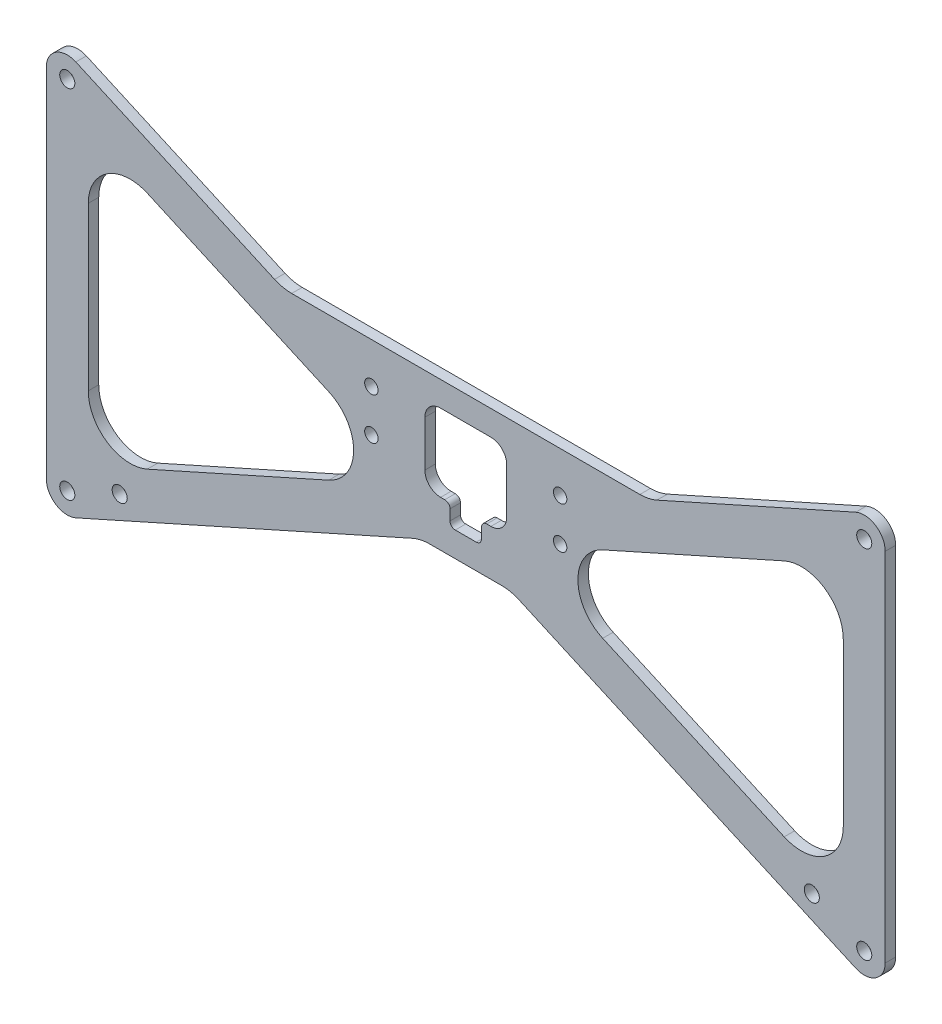
SolidWorks part; units mm, degrees
ref_plane "Front Plane" through (0, 0, 0) normal (0, 0, 1) x (1, 0, 0)
ref_plane "Top Plane" through (0, 0, 0) normal (0, 1, 0) x (1, 0, 0)
ref_plane "Right Plane" through (0, 0, 0) normal (1, 0, 0) x (0, 0, -1)
sketch "Sketch1" plane through (0, 0, 0) normal (0, 0, 1) x (1, 0, 0)
  line L0 (-120.65, -53.975) -> (120.65, 53.975) construction
  line L3 (-114.3, -44.1777) -> (-15.5498, 0)
  line L10 (-118.0569, -59.7714) -> (-13.6323, -13.0552)
  line L11 (-120.65, 53.975) -> (120.65, -53.975) construction
  line L12 (-118.0569, 59.7714) -> (-55.4208, 31.75)
  line L13 (-114.3, 44.1777) -> (-15.5498, 0)
  line L14 (55.4208, 31.75) -> (118.0569, 59.7714)
  line L15 (13.6323, -13.0552) -> (118.0569, -59.7714)
  line L16 (15.5498, 0) -> (114.3, 44.1777)
  line L17 (15.5498, 0) -> (114.3, -44.1777)
  line L18 (-127, 53.975) -> (-127, -53.975)
  line L19 (-114.3, 44.1777) -> (-114.3, -44.1777)
  line L20 (127, 53.975) -> (127, -53.975)
  line L21 (114.3, 44.1777) -> (114.3, -44.1777)
  line L24 (-55.4208, 31.75) -> (55.4208, 31.75)
  line L25 (-13.6323, -13.0552) -> (13.6323, -13.0552)
  arc A4 (-127, -53.975) -> (-118.0569, -59.7714) centre (-120.65, -53.975) ccw
  arc A5 (127, 53.975) -> (118.0569, 59.7714) centre (120.65, 53.975) ccw
  arc A6 (-118.0569, 59.7714) -> (-127, 53.975) centre (-120.65, 53.975) ccw
  arc A7 (118.0569, -59.7714) -> (127, -53.975) centre (120.65, -53.975) ccw
  point P2 (0, 0)
  point P9 (0, 0)
  point P13 (0, 0)
  point P26 (0, 0)
  dimension "D1" = 254
  dimension "D3" = 6.35
  dimension "D2" = 107.95
  dimension "D4" = 13.0552
  dimension "D6" = 31.75
extrude "Boss-Extrude1" add sketch "Sketch1" along normal blind 3.175
sketch "Sketch2" plane through (0, 0, 3.175) normal (0, 0, 1) x (1, 0, 0)
  line L0 (127, -53.975) -> (127, 53.975) construction
  line L1 (-127, 53.975) -> (-127, -53.975) construction
  line L2 (-107.3681, -41.0766) -> (-102.1819, -52.6694) construction
  line L3 (-114.3, -44.1777) -> (-15.5498, 0) construction
  line L4 (-118.0569, -59.7714) -> (-13.6323, -13.0552) construction
  circle A0 centre (-120.65, 53.975) radius 2.286
  circle A1 centre (-120.65, -53.975) radius 2.286
  circle A2 centre (120.65, -53.975) radius 2.286
  circle A3 centre (120.65, 53.975) radius 2.286
  arc A4 (-118.0569, 59.7714) -> (-127, 53.975) centre (-120.65, 53.975) ccw construction
  arc A5 (-127, -53.975) -> (-118.0569, -59.7714) centre (-120.65, -53.975) ccw construction
  arc A6 (118.0569, -59.7714) -> (127, -53.975) centre (120.65, -53.975) ccw construction
  arc A7 (127, 53.975) -> (118.0569, 59.7714) centre (120.65, 53.975) ccw construction
  circle A8 centre (104.775, -46.873) radius 2.286
  circle A9 centre (-104.775, -46.873) radius 2.286
  point P24 (-104.775, -46.873)
  dimension "D1" = 4.572
  dimension "D2" = 22.225
  dimension "D3" = 22.225
extrude "Cut-Extrude1" cut sketch "Sketch2" against normal through all
fillet "Fillet1" radius 12.7 10 edges at (114.3, -44.1777, 1.5875) (114.3, 44.1777, 1.5875) (15.5498, 0, 1.5875) (-114.3, -44.1777, 1.5875) (-15.5498, 0, 1.5875) (-114.3, 44.1777, 1.5875) (-55.4208, 31.75, 1.5875) (55.4208, 31.75, 1.5875) (13.6323, -13.0552, 1.5875) (-13.6323, -13.0552, 1.5875)
sketch "Sketch3" plane through (0, 0, 3.175) normal (0, 0, 1) x (1, 0, 0)
  line L1 (-12.3825, 24.2094) -> (12.3825, 24.2094)
  line L2 (-12.3825, 24.2094) -> (-12.3825, 0.8334)
  line L4 (12.3825, 24.2094) -> (12.3825, 0.8334)
  line L8 (-12.3825, 0.8334) -> (-4.7625, 0.8334)
  line L9 (-4.7625, 0.8334) -> (-4.7625, -5.5166)
  line L10 (-4.7625, -5.5166) -> (4.7625, -5.5166)
  line L11 (4.7625, -5.5166) -> (4.7625, 0.8334)
  line L12 (4.7625, 0.8334) -> (12.3825, 0.8334)
  line L13 (52.7095, 31.75) -> (-52.7095, 31.75) construction
  line L14 (0, 0) -> (-4.7625, 0) construction
  line L15 (0, 0) -> (4.7625, 0) construction
  dimension "D1" = 6.35
  dimension "D2" = 24.765
  dimension "D3" = 9.525
  dimension "D4" = 7.5406
  dimension "D5" = 23.3759
  dimension "D6" = 5.5166
extrude "Cut-Extrude2" cut sketch "Sketch3" against normal through all
fillet "Fillet2" radius 1.5875 4 edges at (4.7625, -5.5166, 1.5875) (-4.7625, -5.5166, 1.5875) (4.7625, 0.8334, 1.5875) (-4.7625, 0.8334, 1.5875)
fillet "Fillet3" radius 4.7625 4 edges at (12.3825, 0.8334, 1.5875) (12.3825, 24.2094, 1.5875) (-12.3825, 0.8334, 1.5875) (-12.3825, 24.2094, 1.5875)
sketch "Sketch4" plane through (0, 0, 0) normal (0, 0, -1) x (-1, 0, 0)
  circle A0 centre (28.575, 19.407) radius 2.032
  circle A1 centre (28.575, 6.707) radius 2.032
  circle A2 centre (-28.575, 6.707) radius 2.032
  circle A3 centre (-28.575, 19.407) radius 2.032
  dimension "D1" = 4.064
extrude "Cut-Extrude3" cut sketch "Sketch4" against normal through all
